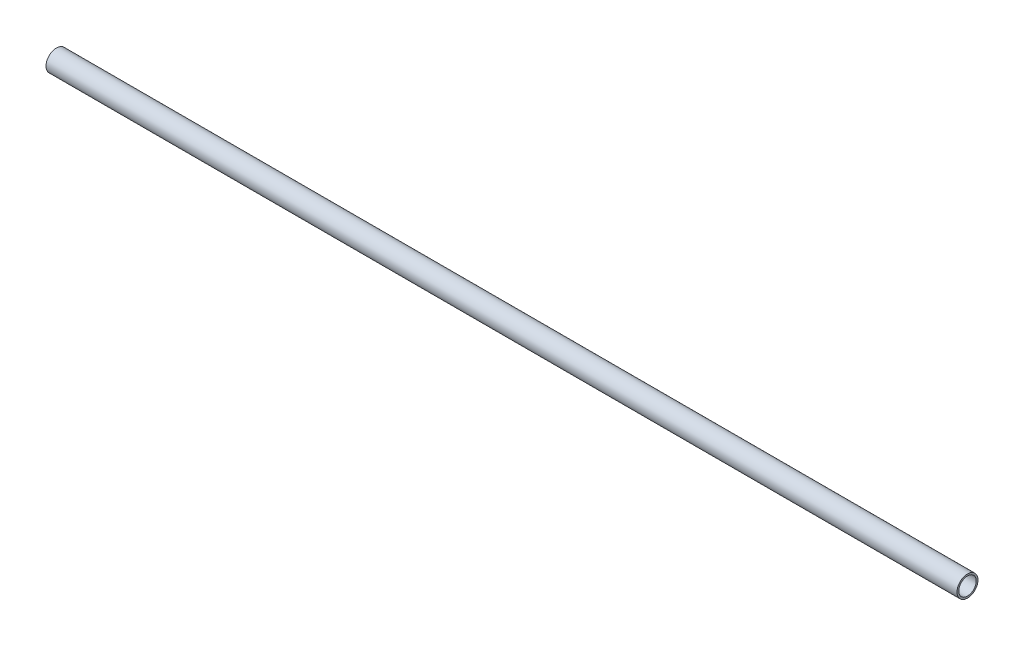
SolidWorks part; units mm, degrees
material "6061-T6 (SS)"
ref_plane "Front Plane" through (0, 0, 0) normal (0, 0, 1) x (1, 0, 0)
ref_plane "Top Plane" through (0, 0, 0) normal (0, 1, 0) x (1, 0, 0)
ref_plane "Right Plane" through (0, 0, 0) normal (1, 0, 0) x (0, 0, -1)
sketch "Sketch1" plane through (0, 0, 0) normal (1, 0, 0) x (0, 0, -1)
  circle A0 centre (0, 0) radius 21.082
  circle A1 centre (0, 0) radius 17.526
  dimension "D1" = 42.164
  dimension "D2" = 35.052
extrude "Boss-Extrude1" add sketch "Sketch1" along normal blind 914.4 and the other way blind 914.4
sketch "Sketch2" plane through (0, 0, 0) normal (0, 0, 1) x (1, 0, 0)
  line L0 (-914.4, 21.082) -> (-914.4, -21.082) construction
  circle A0 centre (-831.85, 0) radius 3.175
  circle A1 centre (-882.65, 0) radius 3.175
  dimension "D1" = 6.35
  dimension "D2" = 31.75
  dimension "D3" = 50.8
extrude "Cut-Extrude1" cut sketch "Sketch2" against normal through all
mirror "Mirror1" about plane through (0, 0, 0) normal (1, 0, 0) of "Cut-Extrude1"
